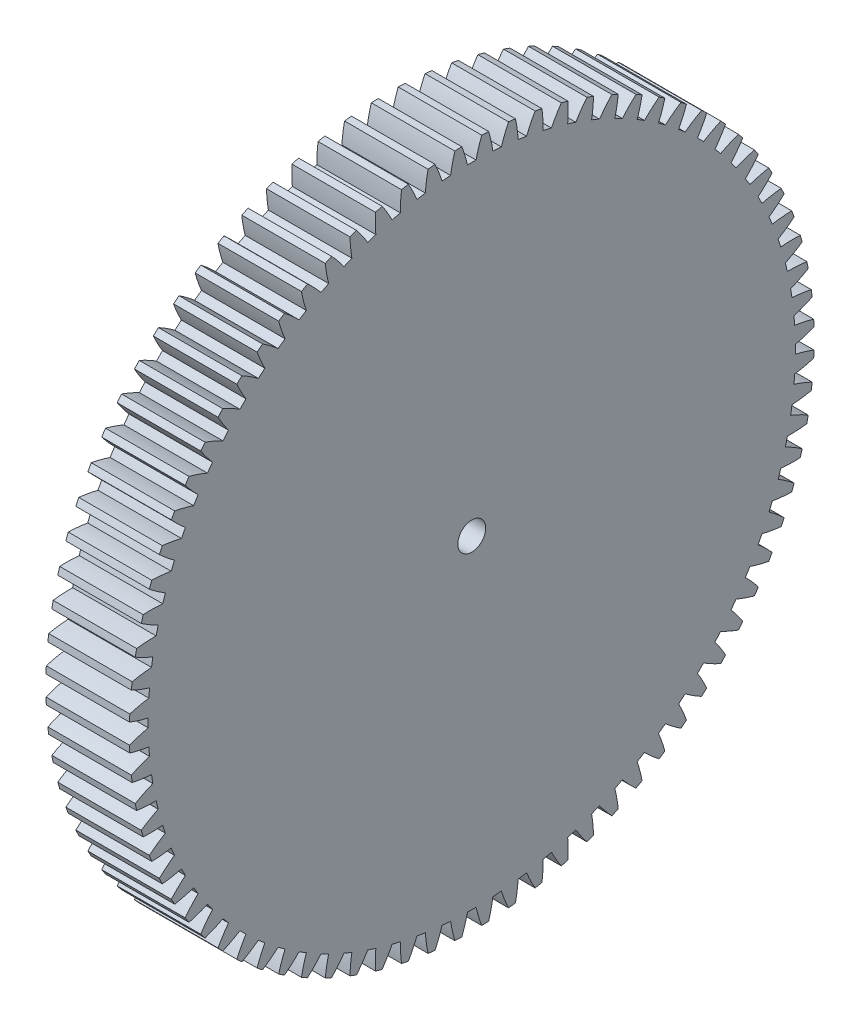
SolidWorks part; units mm, degrees
ref_plane "Plane1" through (0, 0, 0) normal (0, 0, 1) x (1, 0, 0)
ref_plane "Plane2" through (0, 0, 0) normal (0, 1, 0) x (1, 0, 0)
ref_plane "Plane3" through (0, 0, 0) normal (1, 0, 0) x (0, 0, -1)
sketch "HoldingSke" plane through (0, 0, 0) normal (0, 1, 0) x (1, 0, 0)
  line L0 (0, 0) -> (0.1158, -0.6565)
  line L1 (-15, 0) -> (100, 0) construction
  line L2 (0, 0) -> (-2.1039, 2.3779)
  line L3 (0, 0) -> (-11.863, 4.5341)
  line L4 (0, 0) -> (1.4996, 8.5048)
  line L5 (0, 0) -> (-46.8476, -17.4728)
  line L6 (0, 0) -> (-12.4344, -8.3896)
  line L7 (-2.1039, 2.3779) -> (8.6586, 51.2059)
  line L8 (-76.2, 54.61) -> (-75.3, 54.61)
  line L9 (-67.7845, 28.3722) -> (-49.3413, 33.142)
  line L10 (-76.2, 71.12) -> (104.1128, 71.12)
  line L11 (0, 0) -> (-15, 0)
  line L12 (-76.2, 101.6) -> (-76.147, 101.6)
  line L13 (24.9733, 27.94) -> (52.9518, 28.4284)
  line L14 (24.9733, 27.94) -> (24.9743, 27.94)
  line L15 (24.9733, 27.94) -> (100.4006, 29.5858)
  line L16 (-63.627, -1.5) -> (-12.827, -1.5)
  circle A0 centre (0, 0) radius 2.5
  circle A1 centre (0, 0) radius 37.5
  circle A2 centre (0, 0) radius 37.5
  circle A3 centre (0, 0) radius 2.5
  dimension "Num_teeth" = 80
  dimension "Pitch_radius" = 180.3128
  dimension "Width" = 15
  dimension "Thickness" = 15
sketch "BasProSke" plane through (0, 0, 0) normal (0, 1, 0) x (1, 0, 0)
  line L0 (-10, 0) -> (60, 0) construction
  line L1 (0, 0) -> (0, 61.5)
  line L2 (0, 0) -> (15, 0)
  line L3 (15, 0) -> (15, 61.5)
  line L4 (15, 61.5) -> (0, 61.5)
  dimension "Thickness" = 15
  dimension "Diameter" = 123
revolve "Base-Revolve" add sketch "BasProSke" angle 360 about L0
sketch "TooCutSke" plane through (0, 0, 0) normal (1, 0, 0) x (0, 0, -1)
  line L1 (0, 0) -> (0, 107) construction
  line L2 (0, 0) -> (-1.2708, 59.9865) construction
  line L3 (0, 0) -> (-4.7104, 119.8879) construction
  line L4 (-1.2708, 59.9865) -> (-2.3552, 59.9439) construction
  arc A0 (0.768, 58.1189) -> (-0.768, 58.1189) centre (0, 0) ccw
  arc A1 (1.8001, 61.4991) -> (-1.8001, 61.4991) centre (0, 0) ccw
  circle A2 centre (0, 0) radius 60 construction
  circle A3 centre (0, 0) radius 58.0889 construction
  arc A4 (-0.768, 58.1189) -> (-1.8001, 61.4991) centre (-24.1755, 52.8191) ccw
  arc A5 (1.8001, 61.4991) -> (0.768, 58.1189) centre (24.1755, 52.8191) ccw
extrude "ToothCut" cut sketch "TooCutSke" along normal through all
fillet "Breaks" [suppressed] radius 0.03 tangent propagation no
fillet "RootFillets" [suppressed] radius 0.376
pattern_circular "TeethCuts" count 80 over 360 about axis through (-10, 0, 0) along (1, 0, 0) of "ToothCut", "RootFillets", "Breaks"
sketch "HubNeaOneSke" plane through (0, 0, 0) normal (-1, 0, 0) x (0, 0, 1)
  circle A0 centre (0, 0) radius 37.5
  dimension "Diameter" = 75
extrude "HubNearOne" [suppressed] add sketch "HubNeaOneSke" along normal blind 35.0001
sketch "HubNeaBotSke" plane through (0, 0, 0) normal (-1, 0, 0) x (0, 0, 1)
  circle A0 centre (0, 0) radius 37.5
  dimension "Diameter" = 75
extrude "HubNearBoth" [suppressed] add sketch "HubNeaBotSke" along normal blind 17.5
ref_plane "FarPln" through (15, 0, 0) normal (1, 0, 0) x (0, 0, -1)
sketch "HubFarSke" plane through (15, 0, 0) normal (1, 0, 0) x (0, 0, -1)
  circle A0 centre (0, 0) radius 37.5
  dimension "Diameter" = 75
extrude "HubFar" [suppressed] add sketch "HubFarSke" along normal blind 17.5
sketch "BorSke" plane through (0, 0, 0) normal (1, 0, 0) x (0, 0, -1)
  circle A0 centre (0, 0) radius 2.5
  dimension "Diameter" = 5
extrude "Bore" cut sketch "BorSke" along normal mid plane 100.0001
sketch "KeySke" plane through (0, 0, 0) normal (1, 0, 0) x (0, 0, -1)
  line L0 (-1, 0) -> (-1, 3.4)
  line L1 (-1, 3.4) -> (1, 3.4)
  line L2 (1, 3.4) -> (1, 0)
  line L3 (0, 0) -> (0, 34) construction
  line L4 (-1, 0) -> (1, 0)
extrude "Keyway" [suppressed] cut sketch "KeySke" along normal mid plane 100.0001
pattern_circular "Keyway2" [suppressed] count 2 every 90 about axis through (-10, 0, 0) along (1, 0, 0) reverse direction yes
equation "' \"Module@HoldingSke\" = 6.35"
equation "' \"Num_teeth@HoldingSke\" = 12"
equation "' \"Ap@HoldingSke\" =  20"
equation "' \"Ap@HoldingSke\" = 20"
equation "' \"Width@HoldingSke\" = 0.5 * 25.4"
equation "' \"Hub_dia@HoldingSke\"= 1 * 25.4"
equation "' \"Hub_dia@HoldingSke\" = 1 * 25.4"
equation "' \"Overall_len@HoldingSke\" = 1.0 * 25.4"
equation "' \"Bore@HoldingSke\" = 0.75 * 25.4"
equation "' \"T_dim@HoldingSke\" = 0.1 * 25.4"
equation "' \"Width@KeySke\" = 0.25 * 25.4"
equation "' \"Show_teeth@HoldingSke\" = 13"
equation "' \"Backlash@HoldingSke\" = 0.009 * 25.4"
equation "' \"Addendum_fac@HoldingSke\" = 1.0"
equation "' \"Dedendum_fac@HoldingSke\" = 1.25"
equation "' \"Dedendum_add@HoldingSke\" = 0.00005 * 25.4"
equation "' \"Clearance_fac@HoldingSke\" = 0.25"
equation "\"Pitch@HoldingSke\" = 1 / \"Module@HoldingSke\""
equation "\"Overcut_dia@TooCutSke\" = (\"Num_teeth@HoldingSke\" + 2 * \"Addendum_fac@HoldingSke\") / \"Pitch@HoldingSke\" + 0.002 * 25.4"
equation "\"Pitch_dia@TooCutSke\" = \"Num_teeth@HoldingSke\" / \"Pitch@HoldingSke\""
equation "\"Base_dia@TooCutSke\" = \"Num_teeth@HoldingSke\" / \"Pitch@HoldingSke\" * cos((\"Ap@HoldingSke\"  * 3.14159265 / 180))"
equation "\"Root_dia@TooCutSke\" = (\"Num_teeth@HoldingSke\" + 2) / \"Pitch@HoldingSke\" - 2 * (\"Addendum_fac@HoldingSke\" + \"Dedendum_fac@HoldingSke\") / \"Pitch@HoldingSke\" - \"Dedendum_add@HoldingSke\" * 2"
equation "\"Half_ang@TooCutSke\" = 180 / \"Num_teeth@HoldingSke\""
equation "\"Half_CT@TooCutSke\" = \"Num_teeth@HoldingSke\" / \"Pitch@HoldingSke\" * sin((3.14159265 / 2 / \"Num_teeth@HoldingSke\")) / 2 - 7 * \"Backlash@HoldingSke\" / 4"
equation "\"Flank_rad@TooCutSke\" = \"Num_teeth@HoldingSke\" / \"Pitch@HoldingSke\" / 5"
equation "\"Radius@RootFillets\" = \"Clearance_fac@HoldingSke\" / \"Pitch@HoldingSke\" + \"Dedendum_add@HoldingSke\""
equation "\"Break_rad@Breaks\" = 0.02 / \"Pitch@HoldingSke\""
equation "\"Thickness@HoldingSke\" = \"Width@HoldingSke\""
equation "\"OAL@HoldingSke\" = \"Thickness@HoldingSke\""
equation "\"MHD@HoldingSke\" = (\"Num_teeth@HoldingSke\" + 2) / \"Pitch@HoldingSke\" - 2 * (\"Addendum_fac@HoldingSke\" + \"Dedendum_fac@HoldingSke\")  / \"Pitch@HoldingSke\" - \"Dedendum_add@HoldingSke\" * 2"
equation "\"MBD@HoldingSke\" = (\"Num_teeth@HoldingSke\" + 2) / \"Pitch@HoldingSke\" - 2 * (\"Addendum_fac@HoldingSke\" + \"Dedendum_fac@HoldingSke\")  / \"Pitch@HoldingSke\" - \"Dedendum_add@HoldingSke\" * 2 - 0.002 * 25.4"
equation "\"MHD@HoldingSke\" = ((sgn( \"MHD@HoldingSke\" - \"Hub_dia@HoldingSke\" )-1)*( \"MHD@HoldingSke\" - \"Hub_dia@HoldingSke\" ))/-2+ \"Hub_dia@HoldingSke\""
equation "\"MBD@HoldingSke\" = ((sgn( \"MBD@HoldingSke\" - \"Bore@HoldingSke\" )-1)*( \"MBD@HoldingSke\" - \"Bore@HoldingSke\" ))/-2+ \"Bore@HoldingSke\""
equation "\"OAL@HoldingSke\" = ((sgn( \"OAL@HoldingSke\" - \"Overall_len@HoldingSke\" )+1)*( \"OAL@HoldingSke\" - \"Overall_len@HoldingSke\" ))/2 + \"Overall_len@HoldingSke\" + 0.000002 * 25.4"
equation "\"Num_teeth@TeethCuts\" = int( \"Show_teeth@HoldingSke\" ) + 1"
equation "\"Num_teeth@TeethCuts\" = ((sgn( \"Num_teeth@TeethCuts\" - \"Num_teeth@HoldingSke\" )-1)*( \"Num_teeth@TeethCuts\" - \"Num_teeth@HoldingSke\" ))/-2+ \"Num_teeth@HoldingSke\""
equation "\"Num_teeth@TeethCuts\" = ((sgn( \"Num_teeth@TeethCuts\" - 2.0)+1)*( \"Num_teeth@TeethCuts\" - 2.0))/2 +2.0"
equation "\"Angle@TeethCuts\" = 360.0 / \"Num_teeth@HoldingSke\""
equation "\"Diameter@BasProSke\" = (\"Num_teeth@HoldingSke\" + 2 * \"Addendum_fac@HoldingSke\") / \"Pitch@HoldingSke\""
equation "\"Thickness@BasProSke\"  = \"Thickness@HoldingSke\""
equation "' \"Fillet_rad@BasProSke\" =  \"Thickness@HoldingSke\" * 0.05"
equation "' \"Fillet_rad@BasProSke\" = \"Thickness@HoldingSke\" * 0.05"
equation "\"MHD@HoldingSke\" = ((sgn( \"MHD@HoldingSke\" - \"Root_dia@TooCutSke\" )-1)*( \"MHD@HoldingSke\" - \"Root_dia@TooCutSke\" ))/-2+ \"Root_dia@TooCutSke\""
equation "\"Diameter@HubNeaOneSke\" = \"MHD@HoldingSke\""
equation "\"Length@HubNearOne\" = \"OAL@HoldingSke\" - \"Thickness@BasProSke\""
equation "\"Diameter@HubNeaBotSke\" = \"MHD@HoldingSke\""
equation "\"Length@HubNearBoth\" = ( \"OAL@HoldingSke\" - \"Thickness@BasProSke\" ) / 2.0"
equation "\"Thickness@FarPln\" = \"Thickness@BasProSke\""
equation "\"Diameter@HubFarSke\" = \"MHD@HoldingSke\""
equation "\"Length@HubFar\" = ( \"OAL@HoldingSke\" - \"Thickness@BasProSke\" ) / 2.0"
equation "\"Diameter@BorSke\" = \"MBD@HoldingSke\""
equation "\"D1@Bore\" = \"OAL@HoldingSke\" * 2.0"
equation "\"D1@Keyway\" = \"OAL@HoldingSke\" * 2.0"
equation "\"Offset@KeySke\" = \"T_dim@HoldingSke\" + \"MBD@HoldingSke\" / 2.0"
